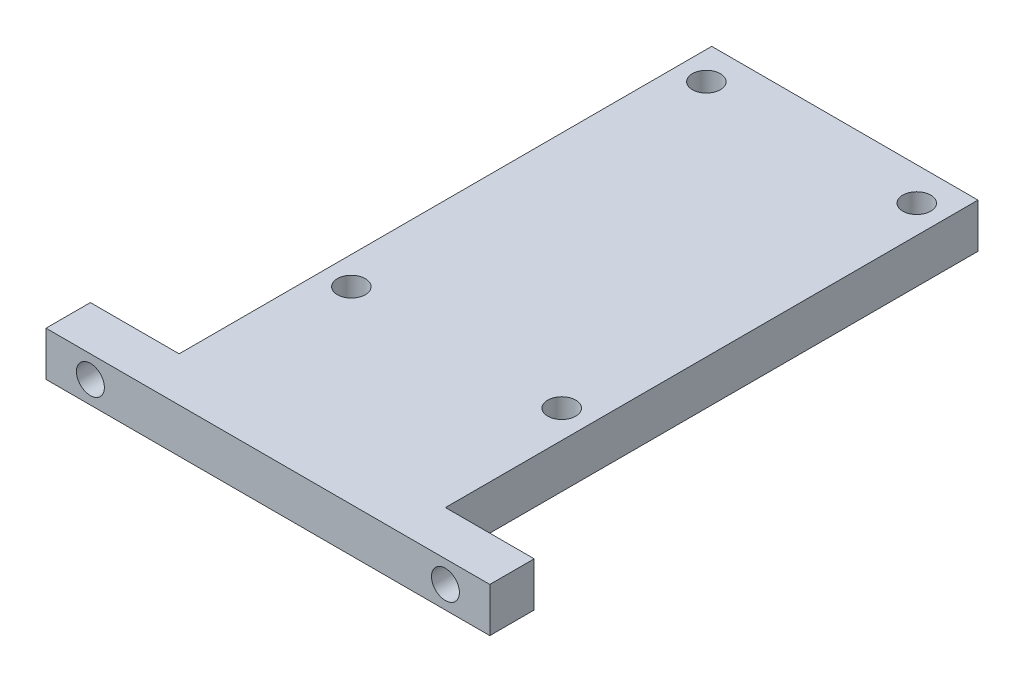
SolidWorks part; units mm, degrees
ref_plane "Front Plane" through (0, 0, 0) normal (0, 0, 1) x (1, 0, 0)
ref_plane "Top Plane" through (0, 0, 0) normal (0, 1, 0) x (1, 0, 0)
ref_plane "Right Plane" through (0, 0, 0) normal (1, 0, 0) x (0, 0, -1)
sketch "Sketch1" plane through (0, 0, 0) normal (0, 1, 0) x (1, 0, 0)
  line L0 (0, 0) -> (63.5, 0)
  line L1 (63.5, 0) -> (63.5, 6.35)
  line L2 (63.5, 6.35) -> (50.8, 6.35)
  line L3 (50.8, 6.35) -> (50.8, 82.55)
  line L4 (50.8, 82.55) -> (12.7, 82.55)
  line L5 (12.7, 82.55) -> (12.7, 6.35)
  line L6 (12.7, 6.35) -> (0, 6.35)
  line L7 (0, 6.35) -> (0, 0)
  dimension "D1" = 12.7
  dimension "D2" = 38.1
  dimension "D3" = 76.2
  dimension "D4" = 6.35
extrude "Boss-Extrude1" add sketch "Sketch1" along normal blind 6.35
sketch "Sketch2" plane through (0, 0, 0) normal (0, 0, 1) x (1, 0, 0)
  line L0 (0, 6.35) -> (0, 0) construction
  line L1 (12.7, 6.35) -> (0, 6.35) construction
  line L2 (63.5, 6.35) -> (50.8, 6.35) construction
  circle A0 centre (6.35, 3.175) radius 2
  circle A1 centre (57.15, 3.175) radius 2
  point P7 (0, 3.175)
  point P11 (6.35, 6.35)
  point P15 (57.15, 6.35)
  dimension "D1" = 4
extrude "Cut-Extrude1" cut sketch "Sketch2" against normal through all both and the other way through all
sketch "Sketch3" plane through (0, 6.35, 0) normal (0, 1, 0) x (1, 0, 0)
  line L0 (50.8, 82.55) -> (12.7, 82.55) construction
  line L1 (50.8, 6.35) -> (50.8, 82.55) construction
  line L2 (12.7, 82.55) -> (12.7, 6.35) construction
  circle A0 centre (46.8, 77.7875) radius 2
  circle A1 centre (16.7, 77.7875) radius 2
  circle A2 centre (16.7, 26.9875) radius 2
  circle A3 centre (46.8, 26.9875) radius 2
  point P10 (0, 0)
  point P11 (0, 0)
  point P12 (0, 0)
  point P13 (0, 0)
  point P18 (0, 0)
  dimension "D1" = 4
  dimension "D2" = 4.7625
  dimension "D3" = 4
  dimension "D4" = 4
  dimension "D5" = 50.8
extrude "Cut-Extrude2" cut sketch "Sketch3" against normal through all both and the other way through all
